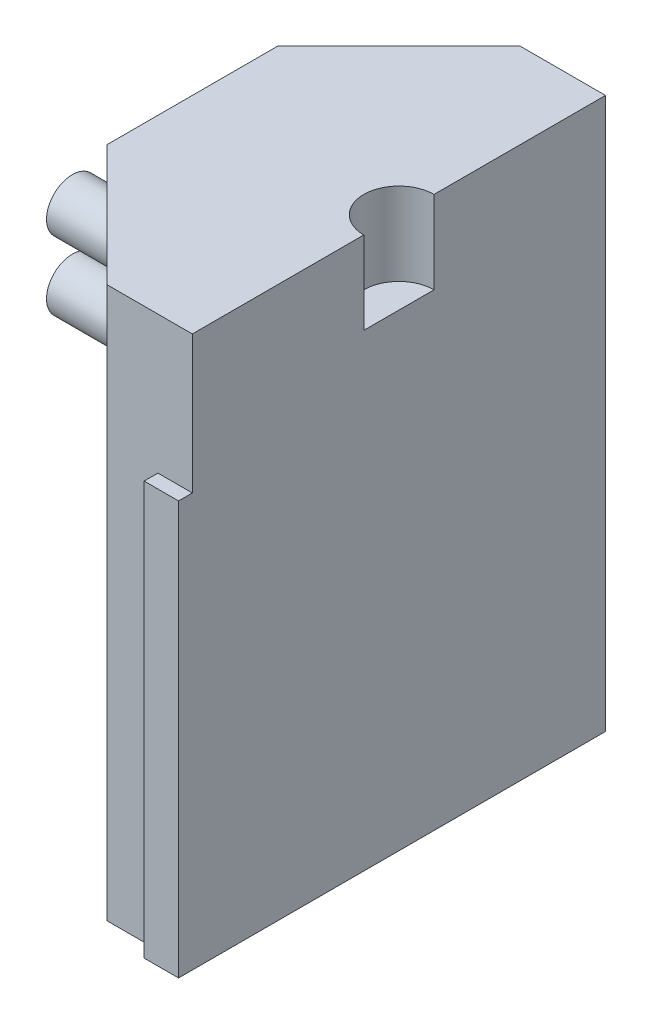
SolidWorks part; units mm, degrees
ref_plane "Front Plane" through (0, 0, 0) normal (0, 0, 1) x (1, 0, 0)
ref_plane "Top Plane" through (0, 0, 0) normal (0, 1, 0) x (1, 0, 0)
ref_plane "Right Plane" through (0, 0, 0) normal (1, 0, 0) x (0, 0, -1)
sketch "Sketch1" plane through (0, 0, 0) normal (0, 1, 0) x (1, 0, 0)
  line L0 (12.4264, -30) -> (30, -12.4264)
  line L1 (30, 12.4264) -> (12.4264, 30)
  line L2 (12.4264, 30) -> (-12.4264, 30)
  line L3 (-12.4264, 30) -> (-30, 12.4264)
  line L4 (-30, 12.4264) -> (-30, -12.4264)
  line L5 (-30, -12.4264) -> (-12.4264, -30)
  line L6 (-12.4264, -30) -> (12.4264, -30)
  line L7 (30, -12.4264) -> (30, 12.4264)
  circle A0 centre (0, 0) radius 30 construction
  dimension "D1" = 60
extrude "Boss-Extrude1" add sketch "Sketch1" along normal blind 80
ref_plane "Plane1" through (0, 40, 0) normal (0, 1, 0) x (1, 0, 0)
sketch "Sketch3" plane through (0, 40, 0) normal (0, 1, 0) x (1, 0, 0)
  line L0 (40, 25) -> (10, 5.1)
  line L1 (10, 5.1) -> (10, -5.1)
  line L2 (10, -5.1) -> (40, -25)
  line L3 (40, 25) -> (40, -25)
  point P2 (10, 0)
  dimension "D1" = 10.2
  dimension "D2" = 30
  dimension "D3" = 10
  dimension "D4" = 50
extrude "Cut-Extrude1" cut sketch "Sketch3" against normal blind 1.1 and the other way blind 1.1
mirror "Mirror1" about plane through (0, 0, 0) normal (1, 0, 0) of "Cut-Extrude1"
sketch "Sketch4" plane through (0, 80, 0) normal (0, 1, 0) x (1, 0, 0)
  line L0 (12.4264, 30) -> (-12.4264, 30) construction
  line L1 (0, 30) -> (30, 30)
  line L2 (0, 30) -> (0, -30)
  line L3 (0, -30) -> (30, -30)
  line L4 (30, 30) -> (30, -30)
  line L5 (-12.4264, -30) -> (12.4264, -30) construction
  line L6 (30, -12.4264) -> (30, 12.4264) construction
extrude "Cut-Extrude2" cut sketch "Sketch4" against normal through all
sketch "Sketch5" plane through (0, 80, 0) normal (0, 1, 0) x (1, 0, 0)
  line L0 (0, 30) -> (0, -30) construction
  circle A0 centre (0, 0) radius 5.1
  dimension "D1" = 10.2
extrude "Cut-Extrude3" cut sketch "Sketch5" against normal blind 12
sketch "Sketch6" plane through (-30, 0, 0) normal (-1, 0, 0) x (0, 0, 1)
  line L0 (12.4264, 80) -> (12.4264, 41.1) construction
  line L1 (-12.4264, 0) -> (12.4264, 0) construction
  line L2 (-5, 20) -> (5, 20)
  line L3 (-5, 20) -> (-5, 10)
  line L4 (-5, 10) -> (5, 10)
  line L5 (5, 20) -> (5, 10)
  line L6 (-12.4264, 80) -> (12.4264, 80) construction
  circle A0 centre (12.4264, 70) radius 3.75
  circle A1 centre (12.4264, 60) radius 3.75
  point P10 (0, 10)
  dimension "D5" = 7.5
  dimension "D1" = 10
  dimension "D2" = 10
  dimension "D3" = 10
  dimension "D4" = 10
extrude "Boss-Extrude2" add sketch "Sketch6" along normal blind 5 and the other way blind 12
sketch "Sketch7" plane through (0, 0, 30) normal (0, 0, 1) x (1, 0, 0)
  line L0 (0, 0) -> (0, 80) construction
  line L1 (0, 0) -> (-5, 0)
  line L2 (0, 0) -> (0, 60)
  line L3 (0, 60) -> (-5, 60)
  line L4 (-5, 0) -> (-5, 60)
  line L5 (-12.4264, 0) -> (0, 0) construction
  dimension "D1" = 5
  dimension "D2" = 60
extrude "Boss-Extrude3" add sketch "Sketch7" along normal blind 2
sketch "Sketch8" plane through (0, 0, 30) normal (0, 0, 1) x (1, 0, 0)
  line L1 (-30, 0) -> (-24.9, 0)
  line L2 (-30, 0) -> (-30, 5.1)
  line L3 (-30, 5.1) -> (-24.9, 5.1)
  line L4 (-24.9, 0) -> (-24.9, 5.1)
  dimension "D1" = 5.1
extrude "Cut-Extrude4" cut sketch "Sketch8" against normal through all
